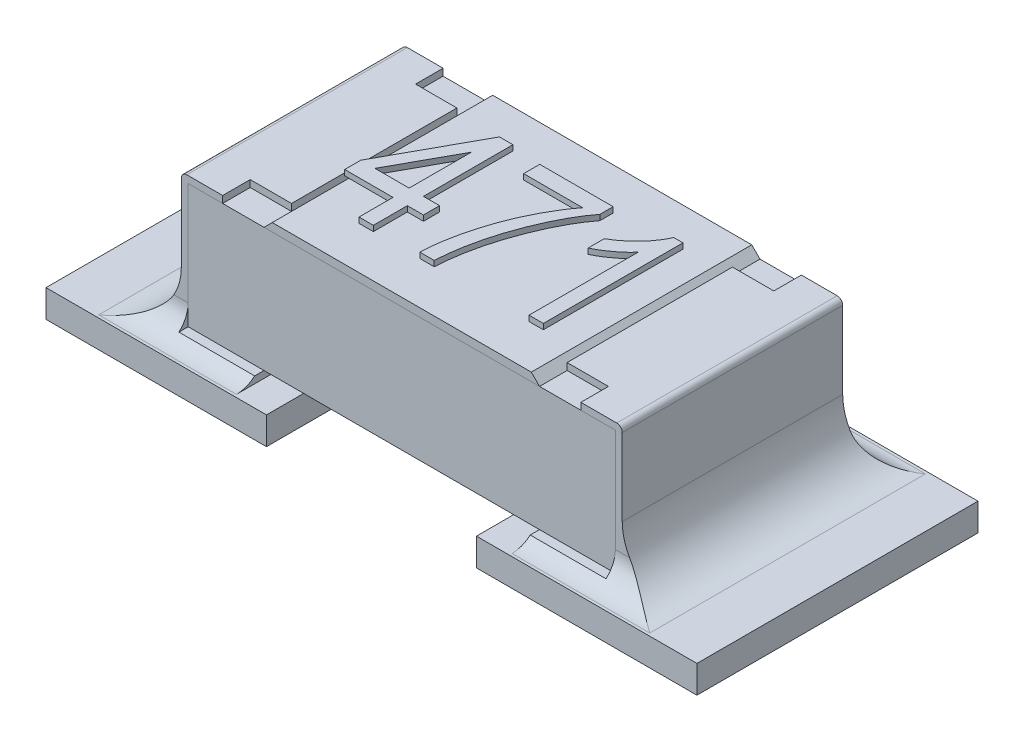
SolidWorks part; units mm, degrees
material "Ceramic Porcelain"
ref_plane "Front Plane" through (0, 0, 0) normal (0, 0, 1) x (1, 0, 0)
ref_plane "Top Plane" through (0, 0, 0) normal (0, 1, 0) x (1, 0, 0)
ref_plane "Right Plane" through (0, 0, 0) normal (1, 0, 0) x (0, 0, -1)
sketch "Sketch1" plane through (0, 0, 0) normal (1, 0, 0) x (0, 0, -1)
  line L0 (0, 55) -> (0, -55) construction
  line L1 (-0.4, 0.575) -> (0.4, 0.575)
  line L2 (-0.4, 0.575) -> (-0.4, 0.125)
  line L3 (-0.4, 0.125) -> (0.4, 0.125)
  line L4 (0.4, 0.575) -> (0.4, 0.125)
  line L5 (55, 0) -> (-55, 0) construction
  dimension "D1" = 0.8
  dimension "D2" = 0.4
  dimension "D3" = 0.45
  dimension "D4" = 0.125
extrude "Boss-Extrude1" add sketch "Sketch1" along normal mid plane 1.55
sketch "Sketch2" plane through (0, 0, 0) normal (0, 0, 1) x (1, 0, 0)
  line L0 (-0.5, 0.6) -> (-0.78, 0.6)
  line L1 (-0.8, 0.58) -> (-0.8, 0.1)
  line L2 (-0.8, 0.1) -> (-0.5, 0.1)
  line L3 (-0.5, 0.1) -> (-0.5, 0.125)
  line L4 (0.775, 0.125) -> (-0.775, 0.125) construction
  line L5 (-0.5, 0.125) -> (-0.775, 0.125)
  line L6 (-0.775, 0.125) -> (-0.775, 0.575)
  line L7 (-0.775, 0.575) -> (-0.5, 0.575)
  line L8 (0.775, 0.575) -> (-0.775, 0.575) construction
  line L9 (-0.5, 0.575) -> (-0.5, 0.6)
  line L11 (0.5, 0.575) -> (0.5, 0.6)
  line L12 (0.5, 0.6) -> (0.78, 0.6)
  line L13 (0.8, 0.58) -> (0.8, 0.1)
  line L14 (0.8, 0.1) -> (0.5, 0.1)
  line L15 (0.5, 0.1) -> (0.5, 0.125)
  line L16 (0.5, 0.125) -> (0.775, 0.125)
  line L17 (0.775, 0.125) -> (0.775, 0.575)
  line L18 (0.775, 0.575) -> (0.5, 0.575)
  arc A0 (0.78, 0.6) -> (0.8, 0.58) centre (0.78, 0.58) cw
  arc A1 (-0.78, 0.6) -> (-0.8, 0.58) centre (-0.78, 0.58) ccw
  point P28 (-0.8, 0.6)
  dimension "D6" = 0.02
  dimension "D1" = 0.025
  dimension "D2" = 0.025
  dimension "D3" = 0.025
  dimension "D4" = 0.3
  dimension "D5" = 0.3
extrude "Boss-Extrude2" add sketch "Sketch2" along normal mid plane 0.8 separate body
sketch "Sketch3" plane through (0, 0.6, 0) normal (0, 1, 0) x (1, 0, 0)
  line L0 (0.5, -0.4) -> (0.5, 0.4) construction
  line L1 (-0.5, 0.4) -> (-0.65, 0.4)
  line L2 (-0.5, 0.4) -> (-0.5, 0.3)
  line L3 (-0.5, 0.3) -> (-0.65, 0.3)
  line L4 (-0.65, 0.4) -> (-0.65, 0.3)
  line L5 (-0.5, -0.4) -> (-0.65, -0.4)
  line L6 (-0.5, -0.4) -> (-0.5, -0.3)
  line L7 (-0.5, -0.3) -> (-0.65, -0.3)
  line L8 (-0.65, -0.4) -> (-0.65, -0.3)
  line L9 (0.5, -0.4) -> (0.65, -0.4)
  line L10 (0.5, -0.4) -> (0.5, -0.3)
  line L11 (0.5, -0.3) -> (0.65, -0.3)
  line L12 (0.65, -0.4) -> (0.65, -0.3)
  line L13 (0.775, -0.4) -> (-0.775, -0.4) construction
  line L15 (0.5, 0.4) -> (0.65, 0.4)
  line L16 (0.5, 0.4) -> (0.5, 0.3)
  line L17 (0.5, 0.3) -> (0.65, 0.3)
  line L18 (0.65, 0.4) -> (0.65, 0.3)
  dimension "D1" = 0.15
  dimension "D2" = 0.1
extrude "Cut-Extrude1" cut sketch "Sketch3" against normal blind 0.025
sketch "Sketch4" plane through (0, 0, 0) normal (0, 0, 1) x (1, 0, 0)
  line L0 (-0.5, 0.575) -> (0.5, 0.575)
  line L1 (0.5, 0.575) -> (0.47, 0.605)
  line L2 (0.47, 0.605) -> (-0.47, 0.605)
  line L3 (-0.47, 0.605) -> (-0.5, 0.575)
  dimension "D1" = 45
  dimension "D2" = 45
  dimension "D3" = 0.03
extrude "Boss-Extrude3" add sketch "Sketch4" along normal mid plane 0.8 separate body
sketch "Sketch7" plane through (0, 0, 0) normal (0, 1, 0) x (1, 0, 0)
  line L0 (0, -0.2833) -> (0, 0.2833) construction
  line L1 (-0.381, -0.51) -> (-1.181, -0.51)
  line L2 (-0.381, -0.51) -> (-0.381, 0.51)
  line L3 (-0.381, 0.51) -> (-1.181, 0.51)
  line L4 (-1.181, -0.51) -> (-1.181, 0.51)
  line L5 (0.381, -0.51) -> (1.181, -0.51)
  line L6 (0.381, -0.51) -> (0.381, 0.51)
  line L7 (0.381, 0.51) -> (1.181, 0.51)
  line L8 (1.181, -0.51) -> (1.181, 0.51)
  line L9 (-0.2833, 0) -> (0.2833, 0) construction
  dimension "D1" = 0.8
  dimension "D2" = 0.381
  dimension "D3" = 0.381
  dimension "D4" = 1.02
  dimension "D5" = 0.51
extrude "Boss-Extrude5" add sketch "Sketch7" along normal blind 0.1
fillet "Fillet3" radius 0.2 1 edges at (-0.8, 0.1, 0)
fillet "Fillet4" radius 0.2 1 edges at (0.8, 0.1, 0)
fillet "Fillet5" radius 0.1 2 edges at (0.75, 0.1, -0.4) (0.75, 0.1, 0.4)
fillet "Fillet6" radius 0.1 2 edges at (-0.75, 0.1, 0.4) (-0.75, 0.1, -0.4)
sketch "Esquisse2" plane through (0, 0.605, 0) normal (0, 1, 0) x (1, 0, 0)
  text T0 "471\r\n" font "Arial Narrow" height 0.5
extrude "Boss.-Extru.1" add sketch "Esquisse2" along normal blind 0.02
